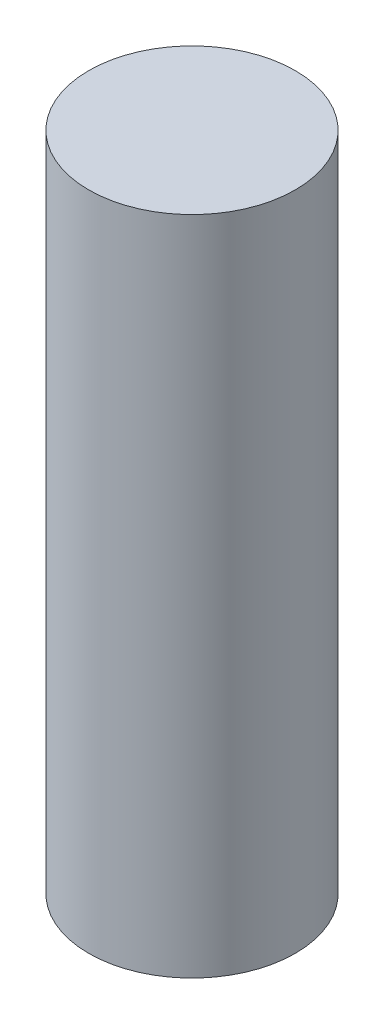
SolidWorks part; units mm, degrees
ref_plane "Front Plane" through (0, 0, 0) normal (0, 0, 1) x (1, 0, 0)
ref_plane "Top Plane" through (0, 0, 0) normal (0, 1, 0) x (1, 0, 0)
ref_plane "Right Plane" through (0, 0, 0) normal (1, 0, 0) x (0, 0, -1)
sketch "Sketch1" plane through (0, 0, 0) normal (0, 1, 0) x (1, 0, 0)
  circle A0 centre (0, 0) radius 12.5
  dimension "D1" = 25
extrude "Boss-Extrude1" add sketch "Sketch1" along normal blind 80
